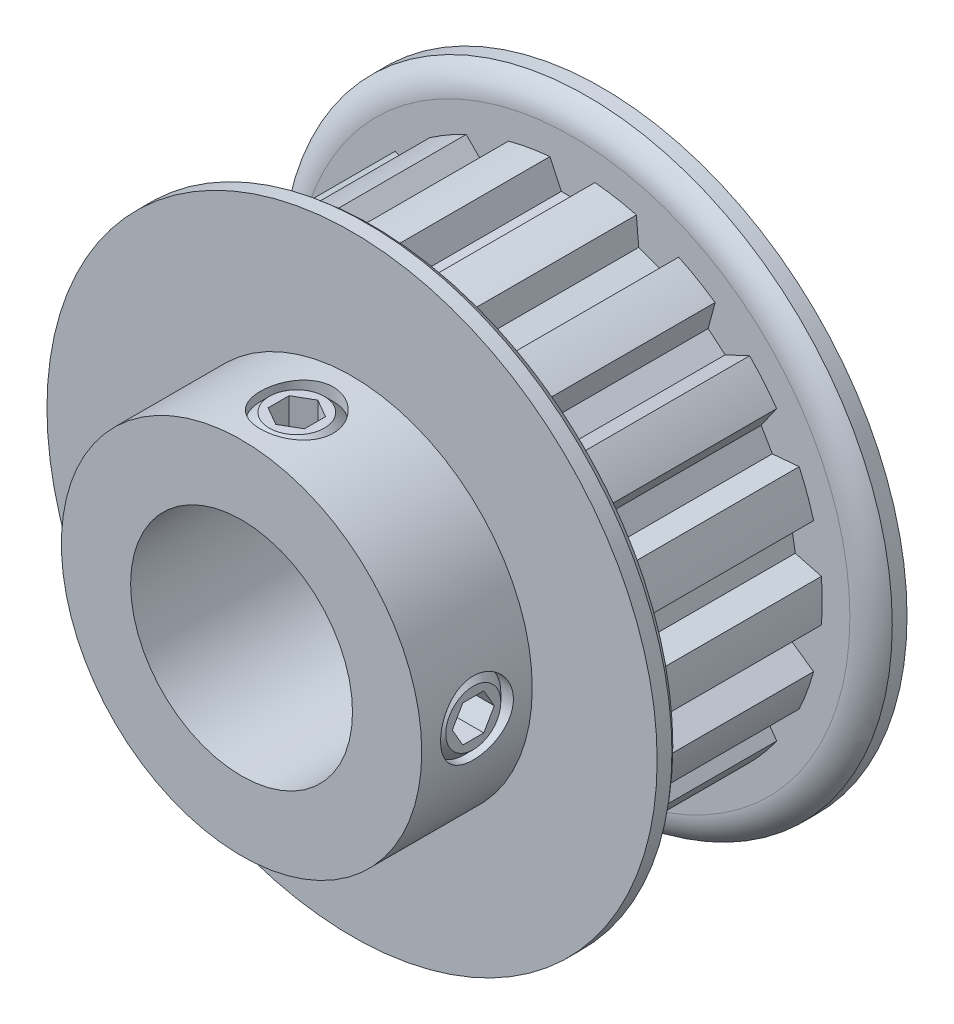
SolidWorks part; units mm, degrees
note: '?' marks a value the reader was unsure of.
ref_plane "Front Plane" through (0, 0, 0) normal (0, 0, 1) x (1, 0, 0)
ref_plane "Top Plane" through (0, 0, 0) normal (0, 1, 0) x (1, 0, 0)
ref_plane "Right Plane" through (0, 0, 0) normal (1, 0, 0) x (0, 0, -1)
sketch "Sketch1" plane through (0, 0, 0) normal (0, 0, 1) x (1, 0, 0)
  line L0 (-1.2878, 14.2421) -> (-0.635, 12.8421)
  line L1 (-0.635, 12.8421) -> (0.635, 12.8421)
  line L2 (0.635, 12.8421) -> (1.2878, 14.2421)
  line L3 (-1.2878, 14.2421) -> (1.2878, 14.2421)
  line L4 (0, 0) -> (0, 12.8421) construction
  line L5 (0, 12.8421) -> (0, 15.1281) construction
  circle A0 centre (0, 0) radius 14.5542 construction
  circle A1 centre (0, 0) radius 17.4625 construction
  circle A2 centre (0, 0) radius 14.3002 construction
  point P6 (0, 14.2421)
  point P11 (0, 14.5542)
  point P13 (0, 17.4625)
  point P14 (0, 14.3002)
  dimension "D1" = 1.4
  dimension "PD" = 29.1084
  dimension "OD" = 34.925
  dimension "D3" = 1.27
  dimension "Gear OD" = 28.6004
  dimension "b" = 50
  dimension "hs" = 2.286
sketch "Sketch2" plane through (0, 0, 0) normal (1, 0, 0) x (0, 0, -1)
  line L0 (-10.3124, 6.35) -> (10.3124, 6.35)
  line L1 (-10.3124, 6.35) -> (-10.3124, 10.3124)
  line L2 (-10.3124, 10.3124) -> (-3.9878, 10.3124)
  line L3 (-3.9878, 10.3124) -> (-3.9878, 17.4625)
  line L4 (-3.9878, 17.4625) -> (-2.2987, 17.4625) construction
  line L5 (-2.2987, 17.4625) -> (-2.2987, 14.3002) construction
  line L6 (-2.2987, 14.3002) -> (8.6233, 14.3002)
  line L7 (8.6233, 14.3002) -> (8.6233, 17.4625) construction
  line L8 (8.6233, 17.4625) -> (10.3124, 17.4625) construction
  line L9 (10.3124, 17.4625) -> (10.3124, 6.35)
  line L10 (-10.3124, 0) -> (10.3124, 0) construction
  line L13 (-3.9878, 17.4625) -> (-3.1432, 17.4625)
  line L14 (-2.2987, 15.8813) -> (-2.2987, 14.3002)
  line L15 (8.6233, 14.3002) -> (8.6233, 15.8813)
  line L16 (9.4679, 17.4625) -> (10.3124, 17.4625)
  arc A0 (-2.2987, 15.8813) -> (-3.1432, 17.4625) centre (-4.2011, 15.8813) ccw
  arc A1 (8.6233, 15.8813) -> (9.4679, 17.4625) centre (10.5257, 15.8813) cw
  point P12 (-2.2987, 15.8813)
  point P14 (-3.1432, 17.4625)
  point P20 (8.6233, 15.8813)
  point P21 (9.4679, 17.4625)
  point P25 (8.6233, 0)
  point P26 (-2.2987, 0)
  dimension "OA" = 20.6248
  dimension "Bore" = 12.7
  dimension "Hub Dia" = 20.6248
  dimension "Outside Width" = 14.3002
  dimension "Inside Width" = 10.922
revolve "Revolve1" add sketch "Sketch2" angle 360 mid plane about L10
sketch "Sketch3" plane through (0, 0, 0) normal (0, 0, 1) x (1, 0, 0)
  line L0 (-0.635, 12.8421) -> (0.635, 12.8421) construction
  line L1 (0.635, 12.8421) -> (1.2878, 14.2421) construction
  line L2 (-1.2878, 14.2421) -> (-0.635, 12.8421) construction
  line L3 (-0.635, 12.8421) -> (0.635, 12.8421)
  line L4 (0.635, 12.8421) -> (1.2878, 14.2421)
  line L5 (-1.2878, 14.2421) -> (-0.635, 12.8421)
  circle A0 centre (0, 0) radius 14.3002 construction
  arc A1 (1.2878, 14.2421) -> (-1.2878, 14.2421) centre (0, 0) ccw
extrude "Cut-Extrude1" cut sketch "Sketch3" against normal up to vertex (8.6233 mm away) from vertex at 2.2987 starting at point (0, 14.3002, 2.2987)
fillet "Fillet1" [suppressed] radius 0.61
pattern_circular "CirPattern1" count 18 over 360 about axis through (0, 0, 0) along (0, 0, 1) of "Cut-Extrude1", "Fillet1"
sketch "Sketch4" plane through (0, 0, 0) normal (0, 1, 0) x (1, 0, 0)
  line L0 (0, -3.9878) -> (0, -10.3124) construction
  circle A0 centre (0, -7.1501) radius 2.0828
  dimension "D1" = 4.1656
extrude "Cut-Extrude2" cut sketch "Sketch4" along normal through all
ref_plane "Plane1" through (0, 0, 7.1501) normal (0, 0, 1) x (1, 0, 0)
sketch "Sketch5" plane through (0, 0, 7.1501) normal (0, 0, 1) x (1, 0, 0)
  line L0 (0, 0) -> (0, 10.3124) construction
  line L1 (1.5748, 10.0999) -> (2.0828, 9.5919)
  line L2 (0, 10.0999) -> (1.5748, 10.0999)
  line L3 (0, 10.0999) -> (0, 6.35)
  line L4 (0, 6.35) -> (1.4478, 6.35)
  line L5 (2.0828, 9.5919) -> (2.0828, 6.985)
  line L6 (1.4478, 6.35) -> (2.0828, 6.985)
  circle A0 centre (0, 0) radius 10.3124 construction
  circle A1 centre (0, 0) radius 6.35 construction
  point P7 (2.0828, 6.35)
  point P9 (2.0828, 10.0999)
revolve "Revolve2" add sketch "Sketch5" angle 360 mid plane about L0
sketch "Sketch6" plane through (0, 10.0999, 0) normal (0, 1, 0) x (1, 0, 0)
  line L1 (0, -5.9476) -> (-1.0414, -6.5488)
  line L2 (-1.0414, -6.5488) -> (-1.0414, -7.7514)
  line L3 (-1.0414, -7.7514) -> (0, -8.3526)
  line L4 (0, -8.3526) -> (1.0414, -7.7514)
  line L5 (1.0414, -7.7514) -> (1.0414, -6.5488)
  line L6 (1.0414, -6.5488) -> (0, -5.9476)
  circle A0 centre (0, -7.1501) radius 1.0414 construction
  dimension "D1" = 2.0828
extrude "Cut-Extrude3" cut sketch "Sketch6" against normal blind 1.5621
pattern_circular "CirPattern2" count 2 every 90 about axis through (0, 0, 0) along (0, 0, 1) of "Cut-Extrude2", "Revolve2", "Cut-Extrude3"
ref_plane "Contact Plane 1" through (0, 0, 10.3124) normal (0, 0, 1) x (1, 0, 0)
ref_plane "Contact Plane 2" through (0, 0, -10.3124) normal (0, 0, -1) x (-1, 0, 0)
ref_axis "Center Axis 1" through (0, 0, -10.3124) along (0, 0, 1)?
equation "\"D1@Sketch6\" = \"D1@Sketch4\"/2"
equation "\"D1@Cut-Extrude3\" = \"D1@Sketch6\"*.75"
